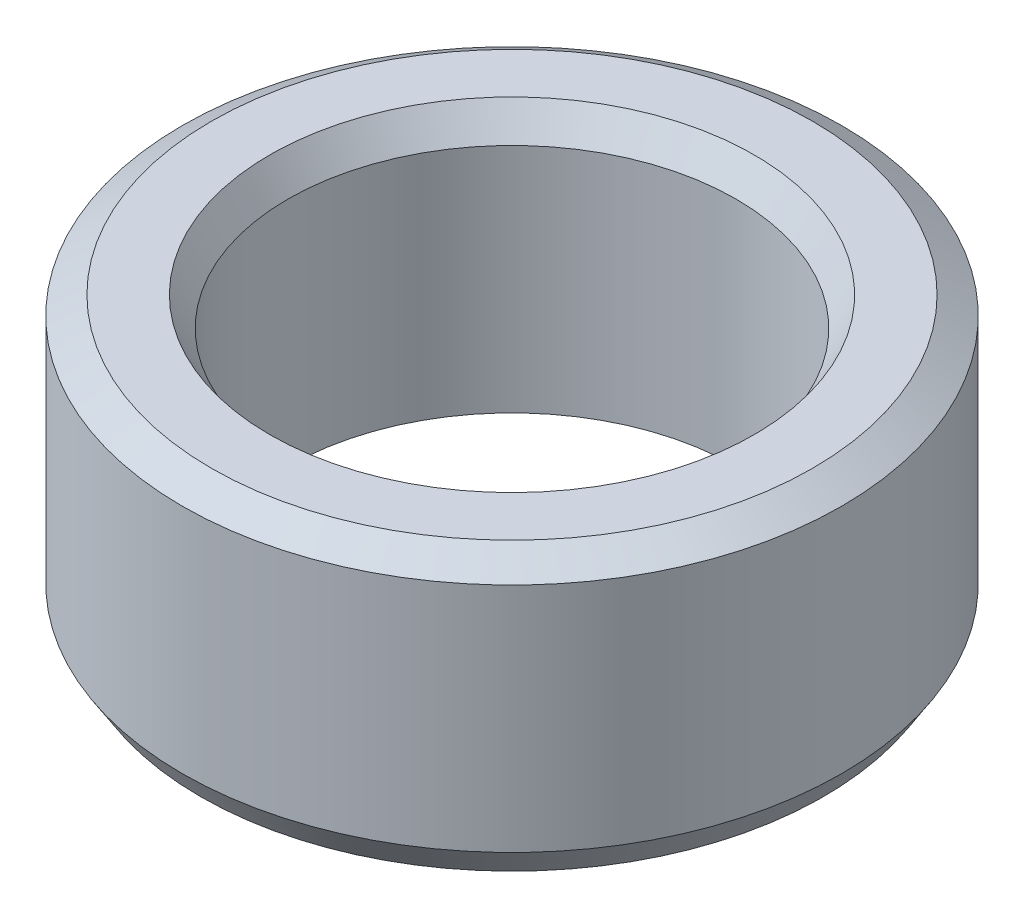
SolidWorks part; units mm, degrees
ref_plane "Front Plane" through (0, 0, 0) normal (0, 0, 1) x (1, 0, 0)
ref_plane "Top Plane" through (0, 0, 0) normal (0, 1, 0) x (1, 0, 0)
ref_plane "Right Plane" through (0, 0, 0) normal (1, 0, 0) x (0, 0, -1)
sketch "Sketch1" plane through (0, 0, 0) normal (0, 1, 0) x (1, 0, 0)
  circle A0 centre (0, 0) radius 55
  dimension "SLEEVE_OD" = 110
extrude "Boss-Extrude1" add sketch "Sketch1" along normal blind 46.5394
sketch "Sketch2" plane through (0, 0, 0) normal (0, 1, 0) x (1, 0, 0)
  circle A0 centre (0, 0) radius 37.3717
  dimension "BORE_D" = 74.7434
extrude "Cut-Extrude1" cut sketch "Sketch2" along normal through all
chamfer "Chamfer1" distance 3.047 angle 57.884 4 edges at (0, 46.5394, 37.3717) (0, 0, 37.3717) (0, 0, 55) (0, 46.5394, 55) first distance on face at (0, 46.5394, 37.3717) first distance on face at (0, 0, 37.3717) first distance on face at (0, 46.5394, 55)
